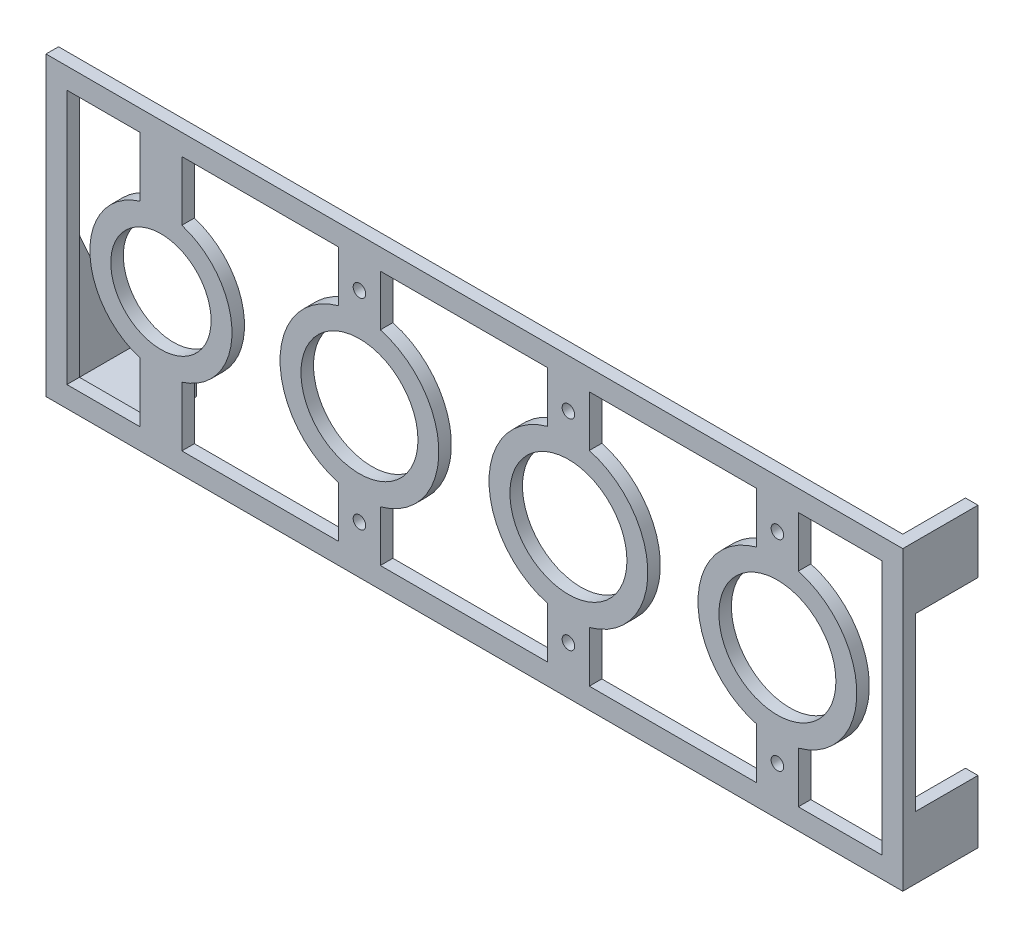
SolidWorks part; units mm, degrees
ref_plane "Front Plane" through (0, 0, 0) normal (0, 0, 1) x (1, 0, 0)
ref_plane "Top Plane" through (0, 0, 0) normal (0, 1, 0) x (1, 0, 0)
ref_plane "Right Plane" through (0, 0, 0) normal (1, 0, 0) x (0, 0, -1)
sketch "Sketch1" plane through (0, 0, 0) normal (0, 0, 1) x (1, 0, 0)
  line L0 (-30, 59.5) -> (-30, 35.5) construction
  line L1 (0, 0) -> (-205, 0)
  line L2 (0, 0) -> (0, 71)
  line L3 (0, 71) -> (-205, 71)
  line L4 (-205, 0) -> (-205, 71)
  line L5 (-30, 35.5) -> (-30, 11.5) construction
  line L6 (-50, 35.5) -> (-10, 35.5) construction
  line L7 (-100, 35.5) -> (-60, 35.5) construction
  line L8 (-150, 35.5) -> (-110, 35.5) construction
  line L9 (-110, 35.5) -> (-100, 35.5) construction
  line L10 (-60, 35.5) -> (-50, 35.5) construction
  line L11 (-195, 35.5) -> (-160, 35.5) construction
  circle A0 centre (-30, 35.5) radius 14
  circle A1 centre (-80, 35.5) radius 14
  circle A2 centre (-130, 35.5) radius 14
  circle A3 centre (-177.5, 35.5) radius 12
  circle A4 centre (-30, 59.5) radius 1.5
  circle A5 centre (-30, 11.5) radius 1.5
  circle A6 centre (-80, 59.5) radius 1.5
  circle A7 centre (-80, 11.5) radius 1.5
  circle A8 centre (-130, 59.5) radius 1.5
  circle A9 centre (-130, 11.5) radius 1.5
  point P29 (-30, 61)
  point P35 (-30, 10)
  dimension "D1" = 28
  dimension "D3" = 24
  dimension "D10" = 3
  dimension "D2" = 48
  dimension "D4" = 40
  dimension "D5" = 35
  dimension "D6" = 10
  dimension "D7" = 10
  dimension "D8" = 10
  dimension "D9" = 10
  dimension "D11" = 10
  dimension "D12" = 10
extrude "Boss-Extrude1" add sketch "Sketch1" along normal blind 3
sketch "Sketch2" plane through (0, 71, 0) normal (0, 1, 0) x (1, 0, 0)
  line L1 (0, 0) -> (-3, 0)
  line L2 (0, 0) -> (0, 15)
  line L3 (0, 15) -> (-3, 15)
  line L4 (-3, 0) -> (-3, 15)
  dimension "D1" = 3
  dimension "D2" = 15
extrude "Boss-Extrude2" add sketch "Sketch2" against normal blind 15
extrude "Boss-Extrude3" add sketch "Sketch2<2>" along normal blind 15 from surface starting at face at (-102.5, 0, 1.5)
sketch "Sketch2<2>" plane through (0, 71, 0) normal (0, 1, 0) x (1, 0, 0) same geometry as "Sketch2"
sketch "Sketch4" plane through (-205, 0, 0) normal (-1, 0, 0) x (0, 0, 1)
  line L1 (0, 0) -> (-15, 0)
  line L2 (0, 0) -> (0, 3)
  line L3 (0, 3) -> (-15, 3)
  line L4 (-15, 0) -> (-15, 3)
  dimension "D1" = 3
  dimension "D2" = 15
extrude "Boss-Extrude4" add sketch "Sketch4" against normal blind 18
sketch "Sketch5" plane through (-205, 0, 0) normal (-1, 0, 0) x (0, 0, 1)
  line L0 (0, 37) -> (-15, 3)
  line L1 (0, 71) -> (0, 3) construction
  line L2 (-15, 3) -> (0, 3)
  line L3 (0, 3) -> (0, 37)
extrude "Boss-Extrude5" add sketch "Sketch5" against normal blind 3
sketch "Sketch6" plane through (0, 0, 3) normal (0, 0, 1) x (1, 0, 0)
  line L12 (-5, 5) -> (-5, 66)
  line L13 (-5, 66) -> (-25, 66)
  line L14 (-200, 66) -> (-200, 5)
  line L15 (-200, 5) -> (-182.5, 5)
  line L18 (-182.5, 51.7481) -> (-182.5, 66)
  line L19 (-182.5, 71) -> (-172.5, 71)
  line L20 (-172.5, 51.7481) -> (-172.5, 66)
  line L22 (-182.5, 19.2519) -> (-182.5, 5)
  line L24 (-172.5, 19.2519) -> (-172.5, 5)
  line L30 (-172.5, 5) -> (-135, 5)
  line L31 (-182.5, 66) -> (-200, 66)
  line L32 (-205, 71) -> (-205, 0) construction
  line L33 (0, 71) -> (-205, 71) construction
  line L34 (-205, 0) -> (0, 0) construction
  line L35 (-135, 66) -> (-172.5, 66)
  line L37 (-135, 53.8303) -> (-135, 66)
  line L39 (-125, 53.8303) -> (-125, 66)
  line L41 (-85, 53.8303) -> (-85, 66)
  line L43 (-75, 53.8303) -> (-75, 66)
  line L45 (-35, 53.8303) -> (-35, 66)
  line L47 (-25, 53.8303) -> (-25, 66)
  line L49 (-85, 17.1697) -> (-85, 5)
  line L51 (-75, 17.1697) -> (-75, 5)
  line L53 (-135, 17.1697) -> (-135, 5)
  line L55 (-125, 17.1697) -> (-125, 5)
  line L57 (-35, 17.1697) -> (-35, 5)
  line L59 (-25, 17.1697) -> (-25, 5)
  line L60 (-85, 66) -> (-125, 66)
  line L62 (0, 0) -> (0, 71) construction
  line L63 (-35, 66) -> (-75, 66)
  line L64 (-25, 5) -> (-5, 5)
  line L65 (-75, 5) -> (-35, 5)
  line L66 (-125, 5) -> (-85, 5)
  arc A0 (-172.5, 19.2519) -> (-172.5, 51.7481) centre (-177.5, 35.5) ccw
  circle A2 centre (-177.5, 35.5) radius 12 construction
  circle A3 centre (-80, 35.5) radius 14 construction
  circle A5 centre (-130, 35.5) radius 14 construction
  circle A6 centre (-30, 35.5) radius 14 construction
  arc A23 (-35, 53.8303) -> (-35, 17.1697) centre (-30, 35.5) ccw
  arc A26 (-85, 53.8303) -> (-85, 17.1697) centre (-80, 35.5) ccw
  arc A27 (-182.5, 51.7481) -> (-182.5, 19.2519) centre (-177.5, 35.5) ccw
  arc A28 (-135, 53.8303) -> (-135, 17.1697) centre (-130, 35.5) ccw
  arc A34 (-125, 17.1697) -> (-125, 53.8303) centre (-130, 35.5) ccw
  arc A38 (-75, 17.1697) -> (-75, 53.8303) centre (-80, 35.5) ccw
  arc A42 (-25, 17.1697) -> (-25, 53.8303) centre (-30, 35.5) ccw
  point P7 (-160.5, 35.5)
  point P18 (-177.5, 35.5)
  point P34 (-123.5, 59.5)
  point P35 (-166.0243, 39.0085)
  point P38 (-130, 11.5)
  point P39 (-61, 35.5)
  point P40 (-80, 11.5)
  point P41 (-11, 35.5)
  point P42 (-30, 11.5)
  point P45 (-23.5, 59.5)
  point P46 (-30, 59.5)
  point P47 (-23.5, 11.5)
  point P48 (-80, 59.5)
  point P49 (-73.5, 11.5)
  point P51 (-73.5, 59.5)
  point P55 (-123.5, 11.5)
  point P56 (-130, 59.5)
  point P57 (-111, 35.5)
  dimension "D5" = 5
  dimension "D6" = 5
  dimension "D4" = 10
  dimension "D2" = 10
  dimension "D1" = 5
  dimension "D3" = 5
  dimension "D7" = 5
  dimension "D8" = 5
extrude "Cut-Extrude1" cut sketch "Sketch6" against normal up to next contours A27 L18 L31 L14 L15 L22 | A28 L37 L35 L20 A0 L24 L30 L53 | A34 L55 L66 L49 A26 L41 L60 L39 | A38 L51 L65 L57 A23 L45 L63 L43 | A42 L59 L64 L12 L13 L47 region at (-15, 5.642, 3) region at (-191.25, 65.3654, 3) region at (-154.3409, 35.5, 3) region at (-105, 35.5, 3) region at (-55, 35.5, 3)
